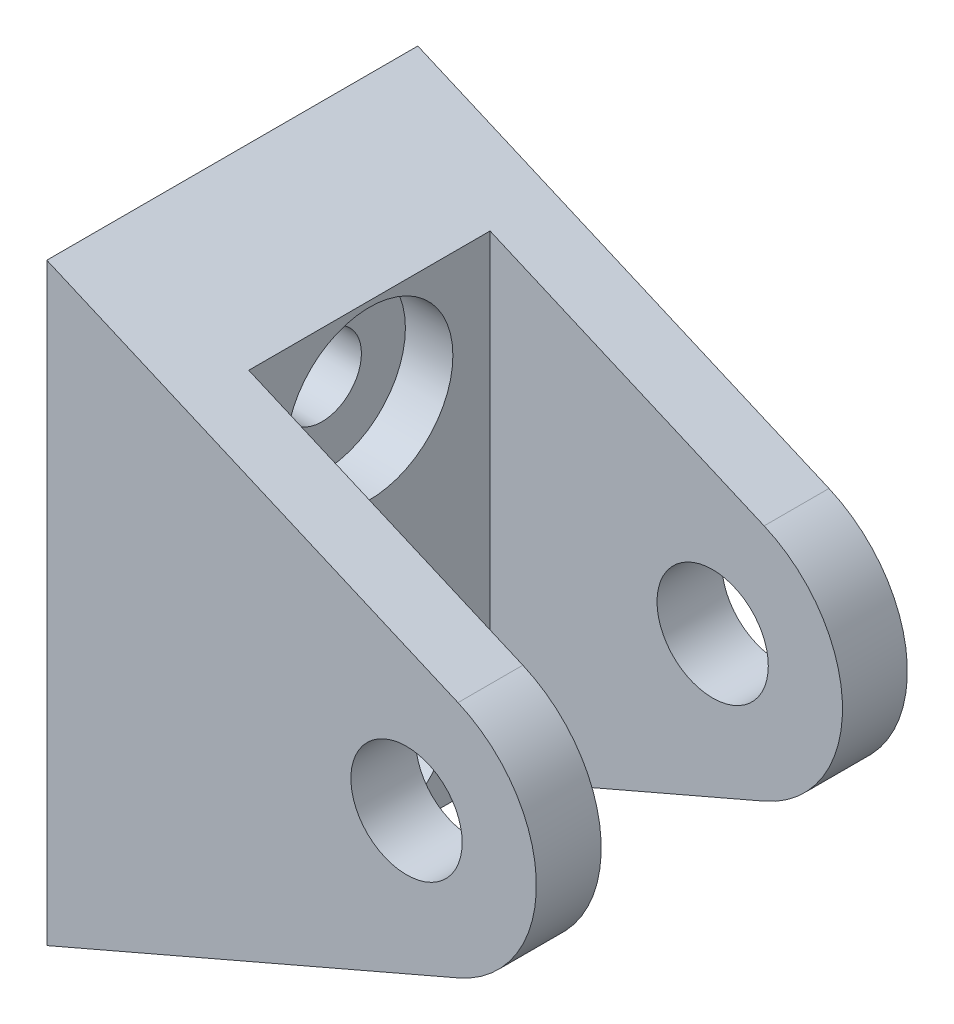
SolidWorks part; units mm, degrees
ref_plane "Front Plane" through (0, 0, 0) normal (0, 0, 1) x (1, 0, 0)
ref_plane "Top Plane" through (0, 0, 0) normal (0, 1, 0) x (1, 0, 0)
ref_plane "Right Plane" through (0, 0, 0) normal (1, 0, 0) x (0, 0, -1)
sketch "Sketch1" plane through (0, 0, 0) normal (0, 1, 0) x (1, 0, 0)
  line L0 (0, 0) -> (43.4837, 0)
  line L1 (43.4837, 0) -> (43.4837, 5.5499)
  line L2 (43.4837, 5.5499) -> (11.7337, 5.5499)
  line L3 (11.7337, 5.5499) -> (11.7337, 26.2001)
  line L4 (11.7337, 26.2001) -> (43.4837, 26.2001)
  line L5 (43.4837, 26.2001) -> (43.4837, 31.75)
  line L6 (43.4837, 31.75) -> (0, 31.75)
  line L7 (0, 31.75) -> (0, 0)
  line L8 (30.7837, 31.75) -> (30.7837, 0) construction
  circle A0 centre (30.7837, 15.875) radius 10.3505 construction
  dimension "D4" = 20.701
  dimension "D1" = 31.75
  dimension "D2" = 31.75
  dimension "D3" = 20.6502
  dimension "D5" = 12.7
extrude "Camber Block Extrude" add sketch "Sketch1" along normal blind 50.8
sketch "Sketch2" plane through (11.7337, 0, 0) normal (1, 0, 0) x (0, 0, -1)
  line L0 (5.5499, 25.4) -> (26.2001, 25.4) construction
  line L1 (5.5499, 50.8) -> (5.5499, 0) construction
  line L2 (26.2001, 50.8) -> (26.2001, 0) construction
  line L3 (15.875, 38.1) -> (15.875, 12.7) construction
  circle A0 centre (15.875, 38.1) radius 3.175 construction
  circle A1 centre (15.875, 12.7) radius 3.175 construction
  point P6 (15.875, 38.1)
  point P7 (15.875, 12.7)
  point P10 (15.875, 25.4)
  point P12 (15.875, 25.4)
  point P17 (15.875, 38.1)
  point P19 (15.875, 12.7)
  dimension "D2" = 6.35
  dimension "D3" = 6.35
  dimension "D1" = 25.4
hole_wizard "CBORE for 1/4 Binding Head Machine Screw1" positions "Sketch2" profile "Sketch3" counterbore size "1/4" standard "ANSI Inch" end condition through all
sketch "Sketch3" plane through (11.7337, 12.7, -15.875) normal (0, 1, 0) x (0, 0, -1)
  line L0 (0, 0) -> (0, 11.7337)
  line L1 (0, 11.7337) -> (3.3782, 11.7337)
  line L3 (3.3782, 11.7337) -> (3.3782, 4.064)
  line L4 (3.3782, 4.064) -> (7.1437, 4.064)
  line L5 (7.1437, 4.064) -> (7.1437, 0)
  line L7 (7.1437, 0) -> (0, 0)
  line L11 (0, -6.35) -> (0, 107.95) construction
  dimension "Thru Hole Dia." = 6.7564
  dimension "Thru Hole Depth" = 11.7337
  dimension "C'Bore Dia." = 14.2875
  dimension "C'Bore Depth" = 4.064
sketch "Sketch5" plane through (0, 0, 0) normal (0, 0, 1) x (1, 0, 0)
  line L0 (0, 25.4) -> (43.4837, 25.4) construction
  line L1 (0, 50.8) -> (0, 0) construction
  line L2 (43.4837, 50.8) -> (43.4837, 0) construction
  line L3 (0, 0) -> (35.1898, 15.1983)
  line L4 (0, 50.8) -> (35.1898, 35.6017)
  line L5 (0, 0) -> (43.4837, 0)
  line L6 (43.4837, 0) -> (43.4837, 50.8)
  line L7 (43.4837, 50.8) -> (0, 50.8)
  circle A0 centre (30.7837, 25.4) radius 4.7625
  arc A1 (35.1898, 15.1983) -> (35.1898, 35.6017) centre (30.7837, 25.4) ccw
  dimension "D1" = 9.525
  dimension "D2" = 6.35
extrude "Cut-Extrude1" cut sketch "Sketch5" against normal up to surface (31.75 mm away) up to face at (21.7418, 25.4, -31.75)
